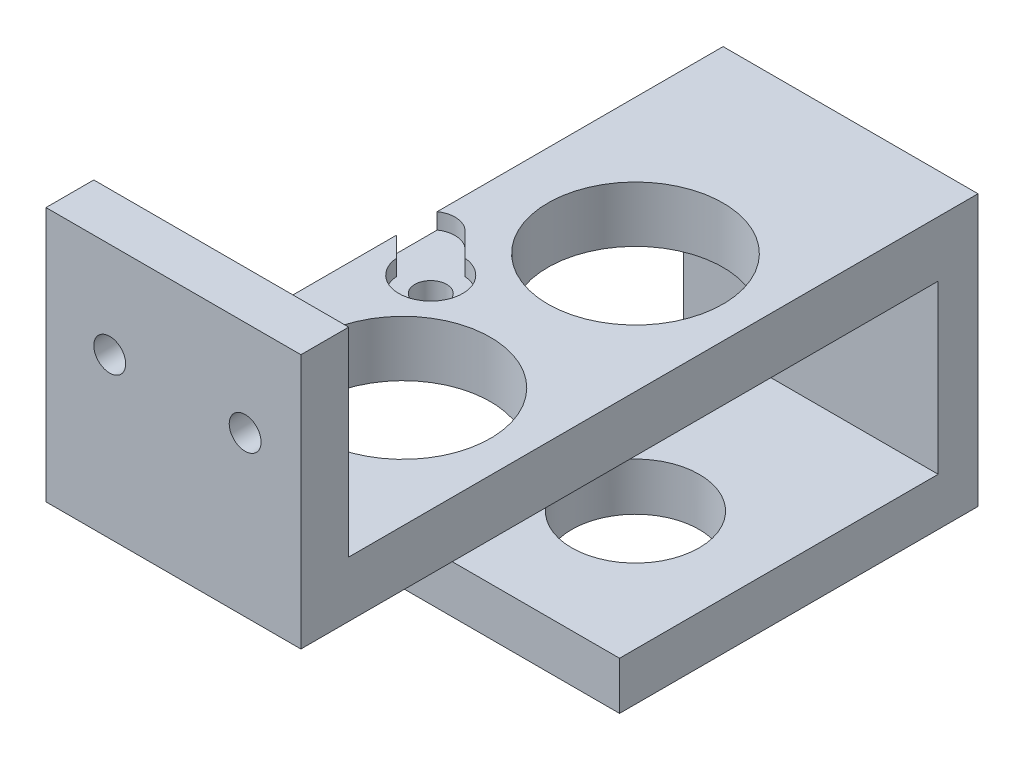
SolidWorks part; units mm, degrees
ref_plane "Front Plane" through (0, 0, 0) normal (0, 0, 1) x (1, 0, 0)
ref_plane "Top Plane" through (0, 0, 0) normal (0, 1, 0) x (1, 0, 0)
ref_plane "Right Plane" through (0, 0, 0) normal (1, 0, 0) x (0, 0, -1)
sketch "Sketch1" plane through (0, 0, 0) normal (0, 1, 0) x (1, 0, 0)
  line L1 (-50.1619, 28.7652) -> (-18.1619, 28.7652)
  line L2 (-50.1619, 28.7652) -> (-50.1619, -56.2348)
  line L3 (-50.1619, -56.2348) -> (-18.1619, -56.2348)
  line L4 (-18.1619, 28.7652) -> (-18.1619, -56.2348)
  dimension "D1" = 85
  dimension "D2" = 32
extrude "Boss-Extrude1" add sketch "Sketch1" along normal blind 7
sketch "Sketch2" plane through (0, 7, 0) normal (0, 1, 0) x (1, 0, 0)
  line L0 (-50.1619, -56.2348) -> (-18.1619, -56.2348) construction
  line L1 (-50.1619, 28.7652) -> (-50.1619, -56.2348) construction
  circle A0 centre (-33.1619, 0.7652) radius 11
  dimension "D1" = 22
  dimension "D2" = 57
  dimension "D3" = 17
extrude "Cut-Extrude1" cut sketch "Sketch2" against normal blind 100
sketch "Sketch3" plane through (0, 7, 0) normal (0, 1, 0) x (1, 0, 0)
  line L0 (-50.1619, 28.7652) -> (-50.1619, -56.2348) construction
  circle A0 centre (-33.1619, -28.4348) radius 11
  circle A1 centre (-33.1619, 0.7652) radius 11 construction
  dimension "D1" = 22
  dimension "D2" = 29.2
  dimension "D3" = 17
extrude "Cut-Extrude2" cut sketch "Sketch3" against normal blind 7
sketch "Sketch4" plane through (0, 7, 0) normal (0, 1, 0) x (1, 0, 0)
  line L0 (-18.1619, -56.2348) -> (-18.1619, 28.7652) construction
  line L1 (-50.1619, -56.2348) -> (-18.1619, -56.2348)
  line L2 (-50.1619, -56.2348) -> (-50.1619, -50.2348)
  line L3 (-50.1619, -50.2348) -> (-18.1619, -50.2348)
  line L4 (-18.1619, -56.2348) -> (-18.1619, -50.2348)
  dimension "D1" = 6
extrude "Boss-Extrude3" add sketch "Sketch4" along normal blind 25
sketch "Sketch5" plane through (0, 0, 50.2348) normal (0, 0, -1) x (-1, 0, 0)
  line L0 (50.1619, 32) -> (50.1619, 7) construction
  line L1 (18.1619, 32) -> (50.1619, 32) construction
  circle A0 centre (42.1619, 20) radius 2
  circle A1 centre (25.1619, 20) radius 2
  dimension "D1" = 4
  dimension "D2" = 4
  dimension "D3" = 8
  dimension "D4" = 17
  dimension "D5" = 0
  dimension "D6" = 12
extrude "Cut-Extrude3" cut sketch "Sketch5" against normal blind 14
sketch "Sketch6" plane through (0, 7, 0) normal (0, 1, 0) x (1, 0, 0)
  circle A0 centre (-43.6619, -14.4348) radius 2
  circle A1 centre (-43.6619, -42.4348) radius 2
  circle A2 centre (-33.1619, -28.4348) radius 11 construction
  dimension "D1" = 4
  dimension "D2" = 4
  dimension "D3" = 28
  dimension "D4" = 10.5
  dimension "D5" = 14
  dimension "D6" = 0
extrude "Cut-Extrude4" cut sketch "Sketch6" against normal blind 14
sketch "Sketch9" plane through (0, 7, 0) normal (0, 1, 0) x (1, 0, 0)
  circle A2 centre (-33.1619, 0.7652) radius 8
  circle A3 centre (-33.1619, 0.7652) radius 11 construction
  dimension "D1" = 16
  dimension "D2" = 0
sketch "Sketch10" plane through (0, 0, 0) normal (0, -1, 0) x (1, 0, 0)
  line L0 (-18.1619, 56.2348) -> (-18.1619, -28.7652) construction
  line L1 (-50.1619, -28.7652) -> (-18.1619, -28.7652)
  line L2 (-50.1619, -28.7652) -> (-50.1619, -23.7652)
  line L3 (-50.1619, -23.7652) -> (-18.1619, -23.7652)
  line L4 (-18.1619, -28.7652) -> (-18.1619, -23.7652)
  dimension "D1" = 5
extrude "Boss-Extrude4" add sketch "Sketch10" along normal blind 27
sketch "Sketch11" plane through (0, 0, -23.7652) normal (0, 0, 1) x (1, 0, 0)
  line L0 (-18.1619, -27) -> (-18.1619, 0) construction
  line L1 (-50.1619, -27) -> (-18.1619, -27)
  line L2 (-50.1619, -27) -> (-50.1619, -21)
  line L3 (-50.1619, -21) -> (-18.1619, -21)
  line L4 (-18.1619, -27) -> (-18.1619, -21)
  dimension "D1" = 6
extrude "Boss-Extrude5" add sketch "Sketch11" along normal blind 40
extrude "Cut-Extrude5" cut sketch "Sketch9" against normal blind 40
sketch "Sketch13" plane through (0, 7, 0) normal (0, 1, 0) x (1, 0, 0)
  circle A0 centre (-43.6619, -14.4348) radius 4
  circle A2 centre (-43.6619, -14.4348) radius 2 construction
  circle A3 centre (-43.6619, -42.4348) radius 4
  circle A4 centre (-43.6619, -42.4348) radius 2 construction
  circle A5 centre (-43.6619, -42.4348) radius 2 construction
  dimension "D1" = 0
  dimension "D2" = 8
  dimension "D3" = 0
  dimension "D4" = 0
  dimension "D5" = 8
extrude "Cut-Extrude6" cut sketch "Sketch13" against normal blind 2
sketch "Sketch15" plane through (0, 7, 0) normal (0, 1, 0) x (1, 0, 0)
  line L0 (-43.6619, -14.4348) -> (-48.4475, -9.6492) construction
  line L1 (-45.8193, -16.5922) -> (-50.6049, -11.8066)
  line L2 (-41.5046, -12.2775) -> (-46.2902, -7.4919)
  line L3 (-43.6619, -42.4348) -> (-48.8836, -47.6565) construction
  line L4 (-41.3168, -44.78) -> (-46.5384, -50.0016)
  line L5 (-46.0071, -40.0897) -> (-51.2288, -45.3113)
  arc A0 (-45.8193, -16.5922) -> (-41.5046, -12.2775) centre (-43.6619, -14.4348) ccw
  arc A1 (-46.2902, -7.4919) -> (-50.6049, -11.8066) centre (-48.4475, -9.6492) ccw
  arc A2 (-41.3168, -44.78) -> (-46.0071, -40.0897) centre (-43.6619, -42.4348) ccw
  arc A3 (-51.2288, -45.3113) -> (-46.5384, -50.0016) centre (-48.8836, -47.6565) ccw
  point P3 (-46.0547, -12.042)
  point P8 (-46.2728, -45.0456)
extrude "Cut-Extrude9" cut sketch "Sketch15" against normal blind 2
